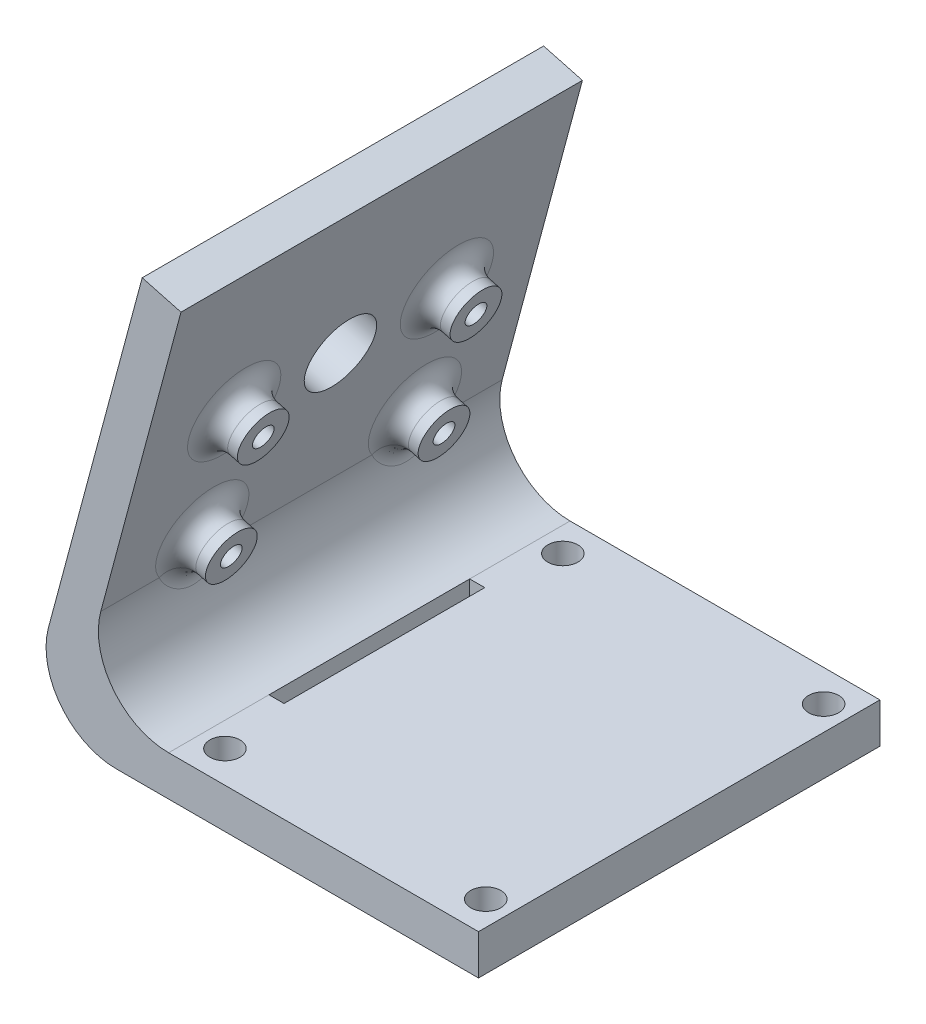
SolidWorks part; units mm, degrees
ref_plane "Piano frontale" through (0, 0, 0) normal (0, 0, 1) x (1, 0, 0)
ref_plane "Piano superiore" through (0, 0, 0) normal (0, 1, 0) x (1, 0, 0)
ref_plane "Piano destro" through (0, 0, 0) normal (1, 0, 0) x (0, 0, -1)
sketch "Schizzo1" plane through (0, 0, 0) normal (0, 0, 1) x (1, 0, 0)
  line L0 (0, 0) -> (-40, 0)
  line L5 (-40, 0) -> (-29.6472, 38.637)
  line L6 (0, -4) -> (-45.2129, -4)
  line L7 (-45.2129, -4) -> (-33.5109, 39.6723)
  line L8 (-33.5109, 39.6723) -> (-29.6472, 38.637)
  line L9 (0, 0) -> (0, -4)
  dimension "D1" = 75
  dimension "D2" = 40
  dimension "D3" = 40
  dimension "D4" = 4
extrude "Estrusione-Estrusione1" add sketch "Schizzo1" along normal blind 40
fillet "Raccordo1" radius 7 2 edges at (-40, 0, 20) (-45.2129, -4, 20)
sketch "Schizzo2" plane through (0, 0, 0) normal (0, 1, 0) x (1, 0, 0)
  line L0 (-30.8774, 0) -> (-30.8774, -40) construction
  line L1 (-30.8774, -10) -> (-29.3774, -10)
  line L2 (-30.8774, -10) -> (-30.8774, -30)
  line L3 (-30.8774, -30) -> (-29.3774, -30)
  line L4 (-29.3774, -10) -> (-29.3774, -30)
  line L5 (0, -40) -> (-30.8774, -40) construction
  dimension "D1" = 20
  dimension "D2" = 10
  dimension "D3" = 1.5
extrude "Taglio-Estrusione1" cut sketch "Schizzo2" against normal blind 40
sketch "Schizzo3" plane through (-41.1842, 11.0353, 0) normal (-0.9659, 0.2588, 0) x (0, 0, 1)
  line L7 (32.6, 23.6021) -> (7.4, -0.3979) construction
  line L8 (32.6, -0.3979) -> (7.4, 23.6021) construction
  line L10 (20, 11.6021) -> (20, -0.3979) construction
  line L11 (9.4029, 1.5096) -> (9.4029, 13.8096) construction
  line L12 (9.4029, 1.5096) -> (19.9029, 13.4096) construction
  line L13 (9.4029, 1.5096) -> (30.5971, 1.5096) construction
  circle A1 centre (9.4029, 1.5096) radius 1.05
  circle A2 centre (30.5971, 1.5096) radius 1.05
  circle A3 centre (9.4029, 13.8096) radius 1.05
  circle A4 centre (30.5971, 13.8096) radius 1.05
  circle A6 centre (19.9029, 13.4096) radius 3.5
  point P8 (20, 11.6021)
  point P13 (9.4029, 1.5096)
  point P24 (20.895, 12.4545)
  dimension "D5" = 2.7659
  dimension "D6" = 2.1
  dimension "D8" = 2.1
  dimension "D11" = 7
  dimension "D1" = 24
  dimension "D2" = 25.2
  dimension "D7" = 12.3
  dimension "D9" = 15.8701
  dimension "D10" = 48.576
extrude "Taglio-Estrusione2" cut sketch "Schizzo3" against normal blind 40
sketch "Schizzo4" plane through (-37.3205, 10, 0) normal (0.9659, -0.2588, 0) x (0, 0, -1)
  circle A0 centre (-30.5971, 13.8096) radius 2.5
  circle A1 centre (-9.4029, 13.8096) radius 2.5
  circle A2 centre (-9.4029, 1.5096) radius 2.5
  circle A3 centre (-30.5971, 1.5096) radius 2.5
  circle A4 centre (-30.5971, 13.8096) radius 1.05
  circle A5 centre (-9.4029, 13.8096) radius 1.05
  circle A6 centre (-9.4029, 1.5096) radius 1.05
  circle A7 centre (-30.5971, 1.5096) radius 1.05
  dimension "D1" = 5
  dimension "D2" = 5
  dimension "D3" = 5
  dimension "D4" = 5
extrude "Estrusione-Estrusione2" add sketch "Schizzo4" along normal blind 3
fillet "Raccordo2" radius 2 4 edges at (-37.5769, 9.0433, 9.4029) (-37.5769, 9.0433, 30.5971) (-34.3934, 20.9242, 9.4029) (-34.3934, 20.9242, 30.5971)
sketch "Schizzo5" plane through (0, 0, 0) normal (0, 1, 0) x (1, 0, 0)
  line L0 (0, 0) -> (-30.8774, -40) construction
  line L1 (0, -40) -> (-30.8774, 0) construction
  circle A0 centre (-2.4442, -36.8336) radius 1.5
  circle A1 centre (-2.4442, -3.1664) radius 1.5
  circle A2 centre (-28.4332, -3.1664) radius 1.5
  circle A3 centre (-28.4332, -36.8336) radius 1.5
  dimension "D1" = 3
  dimension "D2" = 3
  dimension "D3" = 3
  dimension "D4" = 3
  dimension "D5" = 4
  dimension "D6" = 4
  dimension "D7" = 4
  dimension "D8" = 4
extrude "Taglio-Estrusione3" cut sketch "Schizzo5" against normal blind 17
